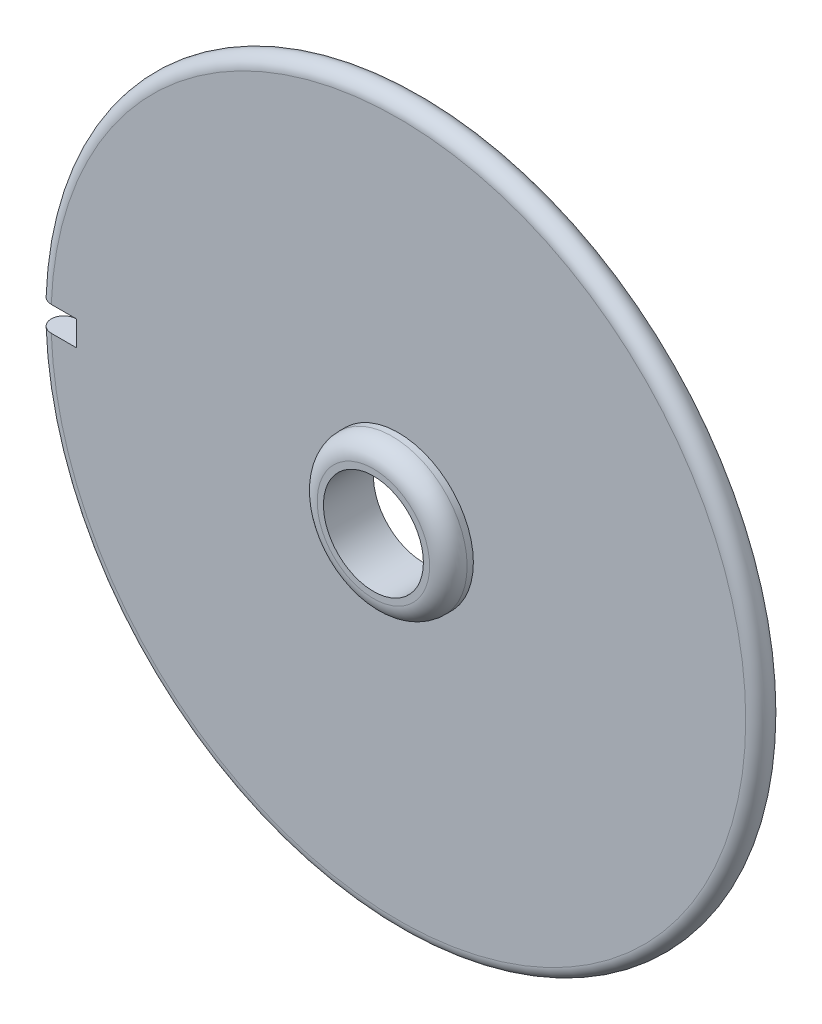
SolidWorks part; units mm, degrees
ref_plane "Front Plane" through (0, 0, 0) normal (0, 0, 1) x (1, 0, 0)
ref_plane "Top Plane" through (0, 0, 0) normal (0, 1, 0) x (1, 0, 0)
ref_plane "Right Plane" through (0, 0, 0) normal (1, 0, 0) x (0, 0, -1)
sketch "Sketch1" plane through (0, 0, 0) normal (0, 0, 1) x (1, 0, 0)
  circle A0 centre (0, -108.5) radius 6 construction
  circle A1 centre (0, -108.5) radius 6
extrude "Boss-Extrude1" add sketch "Sketch1" against normal up to vertex (2 mm away)
sketch "Sketch2" plane through (0, 0, -2) normal (0, 0, -1) x (-1, 0, 0)
  circle A0 centre (0, -108.5) radius 28.8 construction
  circle A1 centre (0, -108.5) radius 28.8
extrude "Boss-Extrude2" add sketch "Sketch2" along normal up to vertex (2 mm away)
sketch "Sketch3" plane through (0, 0, 0) normal (0, 0, 1) x (1, 0, 0)
  circle A0 centre (0, -108.5) radius 4 construction
  circle A1 centre (0, -108.5) radius 4
extrude "Cut-Extrude1" cut sketch "Sketch3" against normal through all
fillet "Fillet1" radius 1.5 1 edges at (6, -108.5, 0)
fillet "Fillet2" radius 1 2 edges at (-28.8, -108.5, -2) (-28.8, -108.5, -4)
sketch "Sketch4" plane through (0, 0, 0) normal (0, 0, 1) x (1, 0, 0)
  line L1 (-31.7826, -107.5) -> (-25.7826, -107.5)
  line L2 (-31.7826, -107.5) -> (-31.7826, -109.5)
  line L3 (-31.7826, -109.5) -> (-25.7826, -109.5)
  line L4 (-25.7826, -107.5) -> (-25.7826, -109.5)
  circle A0 centre (0, -108.5) radius 28.8 construction
  point P4 (-25.7826, -108.5)
  point P5 (-28.7826, -109.5)
  dimension "D1" = 2
  dimension "D2" = 6
extrude "Cut-Extrude2" cut sketch "Sketch4" against normal through all
